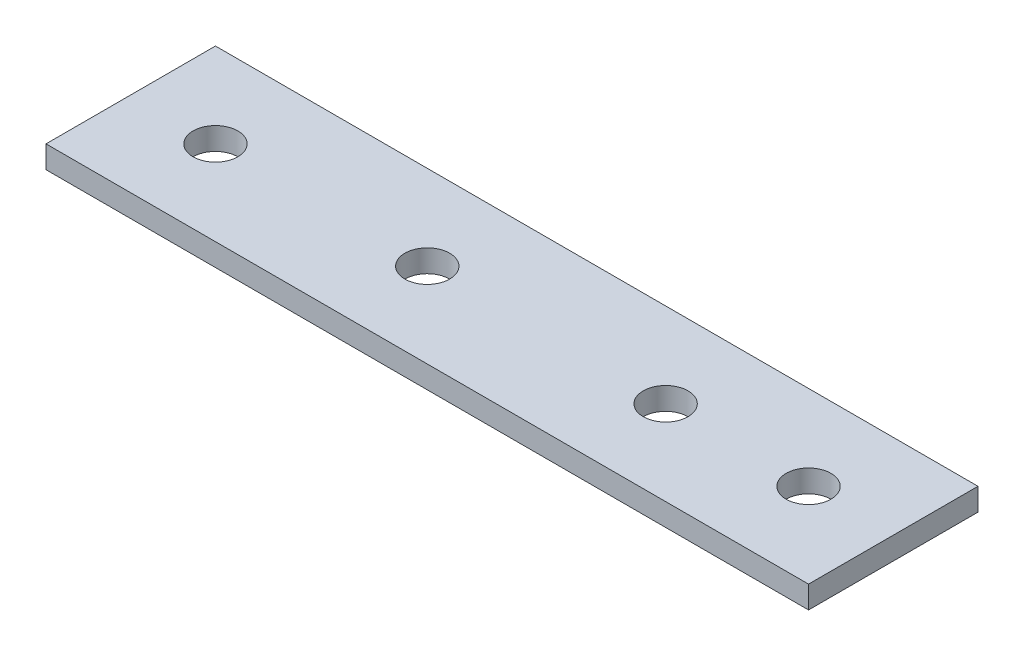
SolidWorks part; units mm, degrees
ref_plane "Front Plane" through (0, 0, 0) normal (0, 0, 1) x (1, 0, 0)
ref_plane "Top Plane" through (0, 0, 0) normal (0, 1, 0) x (1, 0, 0)
ref_plane "Right Plane" through (0, 0, 0) normal (1, 0, 0) x (0, 0, -1)
sketch "Sketch1" plane through (0, 0, 0) normal (0, 1, 0) x (1, 0, 0)
  line L0 (-21, 0) -> (21, 0) construction
  line L1 (27, -6) -> (-27, -6)
  line L2 (27, -6) -> (27, 6)
  line L3 (27, 6) -> (-27, 6)
  line L4 (-27, -6) -> (-27, 6)
  line L5 (27, -6) -> (-27, 6) construction
  line L6 (27, 6) -> (-27, -6) construction
  circle A0 centre (-21, 0) radius 1.5875
  circle A1 centre (21, 0) radius 1.5875
  circle A2 centre (-21, 0) radius 5 construction
  circle A3 centre (-6, 0) radius 1.5875
  circle A4 centre (10.88, 0) radius 1.5875
  point P0 (0, 0)
  point P8 (0, 0)
  dimension "D1" = 3.175
  dimension "D4" = 10
  dimension "D7" = 31.88
  dimension "D2" = 42
  dimension "D3" = 12
  dimension "D5" = 6
  dimension "D6" = 15
extrude "Boss-Extrude1" add sketch "Sketch1" along normal mid plane 1.5875
